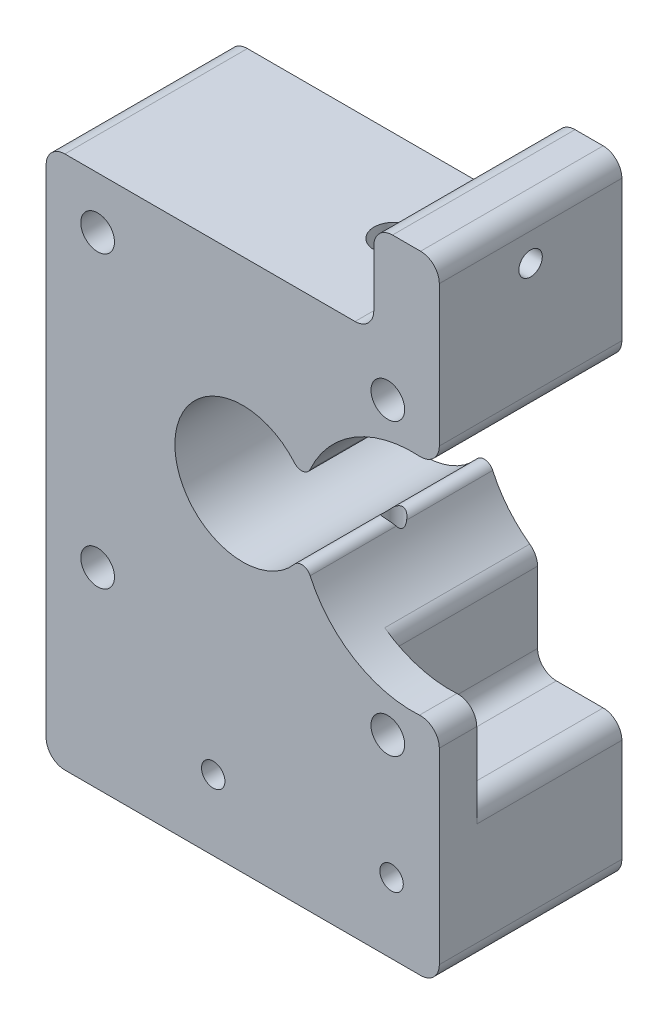
SolidWorks part; units mm, degrees
ref_plane "Front Plane" through (0, 0, 0) normal (0, 0, 1) x (1, 0, 0)
ref_plane "Top Plane" through (0, 0, 0) normal (0, 1, 0) x (1, 0, 0)
ref_plane "Right Plane" through (0, 0, 0) normal (1, 0, 0) x (0, 0, -1)
sketch "Sketch1" plane through (0, 0, 0) normal (0, 0, 1) x (1, 0, 0)
  line L1 (21, 21) -> (-21, 21)
  line L2 (21, 21) -> (21, -21)
  line L3 (21, -21) -> (-21, -21)
  line L4 (-21, 21) -> (-21, -21)
  line L5 (0, -21) -> (0, 21) construction
  line L6 (21, 0) -> (-21, 0) construction
  line L7 (21, 21) -> (14, 21)
  line L8 (21, 21) -> (21, 31)
  line L9 (21, 31) -> (14, 31)
  line L10 (14, 21) -> (14, 31)
  point P0 (0, 0)
  dimension "D1" = 42
  dimension "D2" = 10
  dimension "D3" = 7
extrude "Boss-Extrude1" add sketch "Sketch1" along normal blind 19.5 contours L10 L1 L8 L9 | L3 L4 L1 L2 region at (17.5, 26, 0)
sketch "Sketch2" plane through (0, 0, 19.5) normal (0, 0, 1) x (1, 0, 0)
  circle A0 centre (0, 0) radius 7.25
  dimension "D1" = 14.5
extrude "Cut-Extrude1" cut sketch "Sketch2" against normal blind 22
hole_wizard "M3 Clearance Hole1" positions "Sketch4" profile "Sketch5" hole size "M3" standard "ANSI Metric" end condition through all
sketch "Sketch4" plane through (0, 0, 19.5) normal (0, 0, 1) x (1, 0, 0)
  point P0 (-15.5, 15.5)
  point P2 (15.5, 15.5)
  point P4 (15.5, -15.5)
  point P6 (-15.5, -15.5)
  dimension "D1" = 31
  dimension "D2" = 31
  dimension "D3" = 15.5
  dimension "D4" = 15.5
sketch "Sketch5" plane through (-15.5, 15.5, 19.5) normal (1, 0, 0) x (0, -1, 0)
  line L0 (0, 0) -> (0, 19.5)
  line L1 (0, 19.5) -> (1.8, 19.5)
  line L2 (1.8, 19.5) -> (1.8, 0)
  line L5 (1.8, 0) -> (0, 0)
  line L11 (0, -6.35) -> (0, 107.95) construction
  dimension "Thru Hole Dia." = 3.6
  dimension "Thru Hole Depth" = 19.5
sketch "Sketch6" plane through (0, 0, 19.5) normal (0, 0, 1) x (1, 0, 0)
  circle A0 centre (18.1475, 0) radius 12
  dimension "D1" = 18.1475
  dimension "D2" = 24
extrude "Cut-Extrude2" cut sketch "Sketch6" against normal blind 22
sketch "Sketch7" plane through (0, 0, 0) normal (0, 0, 1) x (1, 0, 0)
  line L0 (21, -11.656) -> (21, -21)
  line L1 (21, -21) -> (12, -21)
  line L2 (21, -21) -> (-21, -21) construction
  line L3 (12, -21) -> (12, -10.3057)
  arc A0 (6.5545, -3.0986) -> (21, -11.656) centre (18.1475, 0) ccw construction
  arc A1 (12, -10.3057) -> (21, -11.656) centre (18.1475, 0) ccw
  dimension "D1" = 9
extrude "Cut-Extrude3" cut sketch "Sketch7" along normal blind 15.5
hole_wizard "M3x0.5 Tapped Hole1" positions "Sketch8" profile "Sketch9" tap size "M3x0.5" standard "ANSI Metric" end condition through all
sketch "Sketch8" plane through (14, 0, 0) normal (-1, 0, 0) x (0, 0, 1)
  line L0 (0, 26) -> (9.75, 26) construction
  line L1 (0, 21) -> (0, 31) construction
  line L2 (9.75, 26) -> (9.75, 31) construction
  line L3 (19.5, 31) -> (0, 31) construction
  point P0 (9.75, 26)
sketch "Sketch9" plane through (14, 26, 9.75) normal (0, 1, 0) x (0, 0, 1)
  line L0 (0, 0) -> (0, 7)
  line L1 (0, 7) -> (1.25, 7)
  line L2 (1.25, 7) -> (1.25, 0)
  line L5 (1.25, 0) -> (0, 0)
  line L11 (0, -6.35) -> (0, 107.95) construction
  dimension "Thru Tap Drill Dia." = 2.5
  dimension "Thru Tap Drill Depth" = 7
cosmetic thread "Hole Thread1" parameters "D2"=3
fillet "Fillet1" radius 1 2 edges at (6.5545, 3.0986, 9.75) (6.5545, -3.0986, 9.75)
hole_wizard "M5x0.8 Tapped Hole1" positions "Sketch10" profile "Sketch11" tap size "M5x0.8" standard "ANSI Metric"
sketch "Sketch10" plane through (0, 21, 0) normal (0, 1, 0) x (1, 0, 0)
  line L0 (-21, -9.75) -> (6.375, -9.75) construction
  line L3 (-21, -19.5) -> (-21, 0) construction
  point P0 (6.375, -9.75)
  dimension "D1" = 6.375
sketch "Sketch11" plane through (6.375, 21, 9.75) normal (1, 0, 0) x (0, 0, 1)
  line L0 (0, 0) -> (0, 22.2618)
  line L1 (0, 22.2618) -> (2.1, 21)
  line L2 (2.1, 21) -> (2.1, 0)
  line L5 (2.1, 0) -> (0, 0)
  line L10 (0, 22.2618) -> (-2.1, 21) construction
  line L11 (0, -6.35) -> (0, 107.95) construction
  dimension "Tap Drill Dia." = 4.2
  dimension "Tap Drill Depth" = 21
  dimension "Drill Angle" = 118
cosmetic thread "Hole Thread2" parameters "D1"=10, "D2"=5
sketch "Sketch12" plane through (0, 21, 0) normal (0, 1, 0) x (1, 0, 0)
  circle A0 centre (6.375, -9.75) radius 1
  dimension "D1" = 2
extrude "Cut-Extrude4" cut sketch "Sketch12" against normal through all
shell "Shell2" [suppressed] thickness 6
other "DeleteFace1" [suppressed]
sketch "Sketch13" [suppressed] plane through (0, 0, 19.5) normal (0, 0, 1) x (1, 0, 0)
  line L0 (-21, -21) -> (-9.9692, -21) construction
  line L1 (-21, -9.9692) -> (-21, -21) construction
  line L2 (-21, 21) -> (-21, 9.9692) construction
  line L3 (-9.9692, 21) -> (-21, 21) construction
  line L4 (-21, -21) -> (-9.9692, -21)
  line L5 (-21, -9.9692) -> (-21, -21)
  line L6 (-21, 21) -> (-21, 9.9692)
  line L7 (-9.9692, 21) -> (-21, 21)
  arc A0 (-9.9692, -21) -> (-21, -9.9692) centre (-15.5, -15.5) ccw construction
  arc A1 (-21, 9.9692) -> (-9.9692, 21) centre (-15.5, 15.5) ccw construction
  arc A2 (-9.9692, -21) -> (-21, -9.9692) centre (-15.5, -15.5) ccw
  arc A3 (-21, 9.9692) -> (-9.9692, 21) centre (-15.5, 15.5) ccw
extrude "Cut-Extrude5" [suppressed] cut sketch "Sketch13" against normal offset from surface (13.5 mm away) 6 up to face at (-13.7, -15.5, 0)
sketch "Sketch14" plane through (0, -21, 0) normal (0, -1, 0) x (1, 0, 0)
  line L0 (7.2046, 0) -> (21, 0) construction
  line L1 (-21, 19.5) -> (21, 19.5)
  line L2 (-21, 19.5) -> (-21, 0)
  line L3 (-21, 0) -> (21, 0)
  line L4 (21, 19.5) -> (21, 0)
  line L5 (0, 0) -> (0, 19.5) construction
  line L6 (-21, 9.75) -> (21, 9.75) construction
  point P120 (0, 9.75)
extrude "Boss-Extrude2" add sketch "Sketch14" along normal blind 15 and the other way blind 0.005
sketch "Sketch15" plane through (0, -20.995, 0) normal (0, 1, 0) x (1, 0, 0)
  circle A1 centre (6.375, -9.75) radius 1
  circle A3 centre (6.375, -9.75) radius 1
  dimension "D1" = 0
extrude "Cut-Extrude6" cut sketch "Sketch15" against normal blind 26.5141
sketch "Sketch16" plane through (0, -20.995, 0) normal (0, 1, 0) x (1, 0, 0)
  line L1 (-15.375, -1.75) -> (-6.875, -1.75)
  line L3 (-15.375, 0) -> (-15.375, -0.75)
  line L4 (-15.375, -0.75) -> (-5.875, -0.75) construction
  line L5 (-5.875, -0.75) -> (-5.875, -3.75) construction
  line L6 (-5.875, -3.75) -> (-0.375, -3.75)
  line L7 (0.625, -3.75) -> (0.625, -11.75) construction
  line L8 (0.625, -11.75) -> (4.875, -11.75) construction
  line L9 (4.875, -11.75) -> (4.875, -3.75) construction
  line L10 (4.875, -3.75) -> (7.875, -3.75) construction
  line L11 (7.875, -3.75) -> (7.875, -11.75) construction
  line L12 (7.875, -11.75) -> (12.125, -11.75) construction
  line L13 (12.125, -11.75) -> (12.125, -3.75) construction
  line L17 (18.625, -3.75) -> (18.625, -0.75) construction
  line L21 (19.625, 0) -> (-15.375, 0)
  line L22 (6.375, -9.75) -> (6.375, -3.75) construction
  line L23 (7.875, -11.75) -> (4.875, -11.75) construction
  line L24 (-6.875, -1.75) -> (-6.875, -3.75)
  line L25 (-0.375, -3.75) -> (-0.375, -12.75)
  line L26 (-0.375, -12.75) -> (4.875, -12.75)
  line L27 (7.875, -12.75) -> (4.875, -12.75)
  line L28 (7.875, -12.75) -> (13.125, -12.75)
  line L29 (13.125, -12.75) -> (13.125, -3.75)
  line L30 (19.625, -3.75) -> (19.625, 0)
  line L32 (-15.375, -0.75) -> (-15.375, -1.75)
  line L33 (-5.875, -3.75) -> (-6.875, -3.75)
  line L34 (18.625, -3.75) -> (19.625, -3.75)
  line L36 (13.125, -3.75) -> (18.625, -3.75)
  line L38 (18.625, -0.75) -> (21, -0.75) construction
  line L39 (19.625, -1.75) -> (21, -1.75) construction
  line L40 (19.625, -3.75) -> (19.625, -1.75) construction
  line L41 (21, 0) -> (14, 0) construction
  point P22 (19.625, 0)
  point P34 (12.9944, -3.8314)
  point P35 (-1.6505, -3.5307)
  point P37 (0, 0)
  point P38 (0, -3.75)
  point P39 (12.585, -3.75)
  dimension "D1" = 24.5
  dimension "D2" = 3
  dimension "D3" = 8
  dimension "D4" = 3
  dimension "D5" = 4.25
  dimension "D6" = 4.25
  dimension "D7" = 6.5
  dimension "D8" = 34
  dimension "D9" = 2
  dimension "D10" = 1
extrude "Cut-Extrude7" cut sketch "Sketch16" against normal blind 11 from offset 2 offset against normal yes
hole_wizard "M3x0.5 Tapped Hole2" positions "Sketch18" profile "Sketch19" tap size "M3x0.5" standard "ANSI Metric" end condition through all
sketch "Sketch18" plane through (0, 0, 3.75) normal (0, 0, -1) x (-1, 0, 0)
  line L0 (3.15, -28.495) -> (-15.9, -28.495) construction
  line L4 (-6.375, -33.995) -> (-6.375, -22.995) construction
  line L8 (0.375, -22.995) -> (-13.125, -22.995) construction
  line L9 (0.375, -33.995) -> (-13.125, -33.995) construction
  point P0 (3.15, -28.495)
  point P2 (-15.9, -28.495)
  point P21 (-6.375, -28.495)
  point P22 (-6.375, -21.995)
  point P25 (-6.375, -32.995)
  dimension "D1" = 19.05
sketch "Sketch19" plane through (-3.15, -28.495, 3.75) normal (1, 0, 0) x (0, 1, 0)
  line L0 (0, 0) -> (0, 15.75)
  line L1 (0, 15.75) -> (1.25, 15.75)
  line L2 (1.25, 15.75) -> (1.25, 0)
  line L5 (1.25, 0) -> (0, 0)
  line L11 (0, -6.35) -> (0, 107.95) construction
  dimension "Thru Tap Drill Dia." = 2.5
  dimension "Thru Tap Drill Depth" = 15.75
cosmetic thread "Hole Thread5" parameters "D2"=3
cosmetic thread "Hole Thread6" parameters "D2"=3
chamfer "Chamfer1" distance 2 angle 60 1 edges at (6.375, -22.995, 10.75) first distance on face at (2.025, -22.995, 4.4)
fillet "Fillet3" radius 2 11 edges at (12, -10.3057, 7.75) (21, -11.656, 17.5) (-21, 21, 9.75) (14, 21, 9.75) (14, 31, 9.75) (21, 31, 9.75) (21, 11.656, 9.75) (-21, -36, 9.75) (21, -36, 9.75) (21, -20.995, 7.75) (12, -20.995, 7.75)
chamfer "Chamfer2" distance 1 angle 60 1 edges at (6.375, -36, 8.75) first distance on face at (6.375, -36, 8.75)
